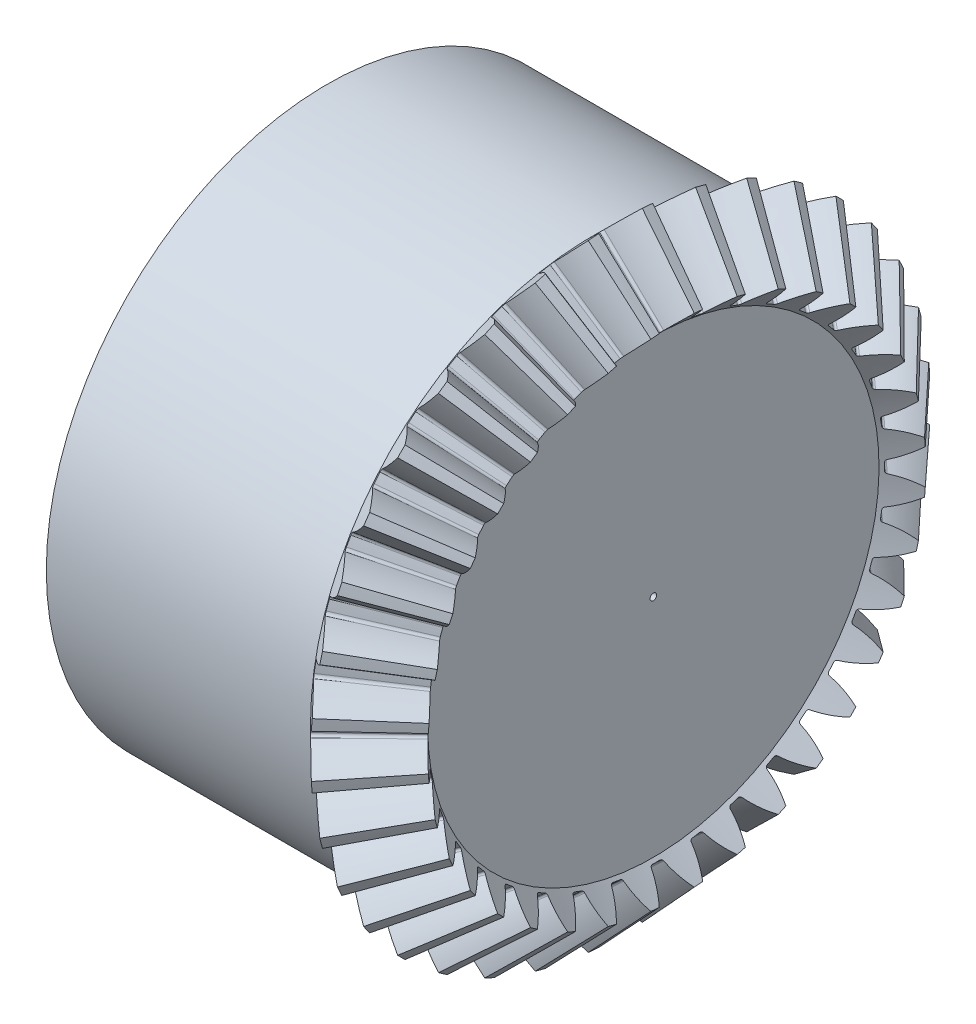
SolidWorks part; units mm, degrees
revolve "Base-Revolve" add sketch "BasProSke" angle 360 about L0 other way angle 5
sketch "BasProSke" plane through (0, 0, 0) normal (0, 1, 0) x (1, 0, 0)
  line L0 (-10, 0) -> (60, 0) construction
  line L1 (0, 0) -> (0, 33.899)
  line L2 (0, 0) -> (7.4837, 0)
  line L3 (7.4837, 0) -> (7.4837, 27.2406)
  line L4 (38.101, 0) -> (-20.321, 58.422) construction
  line L5 (0, 33.899) -> (3.5152, 37.4142)
  line L6 (38.101, 0) -> (-41.3373, 85.9348) construction
  line L7 (38.101, 0) -> (0, 33.899) construction
  line L8 (3.5152, 37.4142) -> (10.3085, 30.0654)
  line L9 (10.3085, 30.0654) -> (7.4837, 27.2406)
  line L10 (2.101, 36) -> (-9.8834, 36) construction
  dimension "D1" = 67.798
  dimension "D2" = 38.101
  dimension "D3" = 50.9117
  dimension "D4" = 2.25
ref_plane "Plane1" through (0, 0, 0) normal (0, 0, 1) x (1, 0, 0)
ref_plane "Plane2" through (0, 0, 0) normal (0, 1, 0) x (1, 0, 0)
ref_plane "Plane3" through (0, 0, 0) normal (1, 0, 0) x (0, 0, -1)
sketch "HoldingSke" plane through (0, 0, 0) normal (0, 1, 0) x (1, 0, 0)
  line L0 (0, 0) -> (0.4045, -0.2939)
  line L1 (-15, 0) -> (100, 0) construction
  line L2 (0, 0) -> (-69.4833, 60.7542)
  line L3 (0, 0) -> (-11.863, 4.5341)
  line L4 (0, 0) -> (6.9867, 5.0761)
  line L5 (0, 0) -> (-65.5867, -24.4619)
  line L6 (0, 0) -> (-10.5278, -7.1032)
  line L7 (-69.4833, 60.7542) -> (-40.5324, 124.4869)
  line L8 (-76.2, 2) -> (-76.1, 2)
  line L9 (-71.009, 38.7566) -> (-53.1078, 45.2721)
  line L10 (-76.2, 71.12) -> (104.1128, 71.12)
  line L11 (0, 0) -> (-10, 0)
  line L12 (-76.2, 101.6) -> (-76.133, 101.6)
  line L13 (24.9733, 27.94) -> (52.9518, 28.4284)
  line L14 (24.9733, 27.94) -> (24.9743, 27.94)
  line L15 (24.9733, 27.94) -> (100.4024, 29.5042)
  line L16 (-69.4833, 60.7542) -> (34.9667, -15.1332)
  circle A0 centre (0, 0) radius 0.4
  circle A1 centre (0, 0) radius 33.899
  circle A2 centre (0, 0) radius 37.5
  circle A3 centre (0, 0) radius 0.4
  dimension "Num_teeth" = 36
  dimension "Pitch_radius" = 180.3128
  dimension "Width" = 10
ref_plane "ToothPln" through (1.7576, 35.6566, 0) normal (-0.7071, 0.7071, 0) x (0, 0, -1)
ref_plane "ToothPln2" through (19.0505, -19.0505, 0) normal (-0.7071, 0.7071, 0) x (0, 0, 1)
sketch "TooCutSke" plane through (1.7576, 35.6566, 0) normal (-0.7071, 0.7071, 0) x (0, 0, -1)
  line L2 (0, 35.5144) -> (147.7559, -1653.3434) construction
  line L3 (0, 35.5144) -> (80.057, -1759.7192) construction
  line L4 (0, -15.621) -> (0, 105.791) construction
  line L6 (-24.765, -2.4856) -> (21.082, -2.4856) construction
  line L7 (3.1376, -0.3486) -> (1.6023, -0.4171) construction
  arc A0 (-3.0922, -3.1221) -> (3.0922, -3.1221) centre (0, 35.5144) ccw
  arc A1 (-0.5546, 1.8959) -> (0.5546, 1.8959) centre (0, 35.5144) ccw
  circle A2 centre (0, 35.5144) radius 36 construction
  circle A3 centre (0, 35.5144) radius 33.8289 construction
  arc A4 (0.9263, 1.6113) -> (0.5546, 1.8959) centre (0.5608, 1.519) ccw
  arc A5 (0.9263, 1.6113) -> (3.0922, -3.1221) centre (14.8879, 5.1376) ccw
  arc A6 (-3.0922, -3.1221) -> (-0.9263, 1.6113) centre (-14.8879, 5.1376) ccw
  arc A7 (-0.5546, 1.8959) -> (-0.9263, 1.6113) centre (-0.5608, 1.519) ccw
  ellipse E0 centre (0, 23.9702) end of major axis (37.4142, 23.9702) minor radius 26.4558 construction
sketch "TooCutSke2" plane through (19.0505, -19.0505, 0) normal (-0.7071, 0.7071, 0) x (0, 0, 1)
  line L0 (0, 0) -> (0, 68.072) construction
  line L2 (21.082, 23.9702) -> (-20.32, 23.9702) construction
  circle A0 centre (0, 26.9415) radius 0.0127
  ellipse E1 centre (0, 0) end of major axis (-33.899, 0) minor radius 23.9702 construction
loft "ToothCut" cut profiles "TooCutSke2", "TooCutSke"
pattern_circular "TeethCuts" count 36 every 10 about axis through (-10, 0, 0) along (1, 0, 0) of "ToothCut"
sketch "HubSke" plane through (0, 0, 0) normal (-1, 0, 0) x (0, 0, 1)
  circle A0 centre (0, 0) radius 33.899
  dimension "Diameter" = 67.798
extrude "Hub" add sketch "HubSke" along normal blind 31.8991
sketch "BorSke" plane through (0, 0, 0) normal (1, 0, 0) x (0, 0, -1)
  circle A0 centre (0, 0) radius 0.4
  dimension "Diameter" = 0.8
extrude "Bore" cut sketch "BorSke" along normal mid plane 140.0001
sketch "KeySke" plane through (0, 0, 0) normal (1, 0, 0) x (0, 0, -1)
  line L0 (-0.05, 0) -> (-0.05, 0.5)
  line L1 (-0.05, 0.5) -> (0.05, 0.5)
  line L2 (0.05, 0.5) -> (0.05, 0)
  line L3 (0, 0) -> (0, 34) construction
  line L4 (-0.05, 0) -> (0.05, 0)
  dimension "Offset" = 0.5
extrude "Keyway" [suppressed] cut sketch "KeySke" along normal mid plane 140.0001
pattern_circular "Keyway2" [suppressed] count 2 every 90 about axis through (-10, 0, 0) along (1, 0, 0) reverse direction yes
equation "' \"Module@HoldingSke\" = 6.35"
equation "' \"Num_teeth@HoldingSke\" = 12"
equation "' \"Mating_teeth@HoldingSke\" = 12"
equation "' \"Ap@HoldingSke\" =  20"
equation "' \"Ap@HoldingSke\" = 20"
equation "' \"Width@HoldingSke\" = 0.5 * 25.4"
equation "' \"Hub_dia@HoldingSke\"= 2 * 25.4"
equation "' \"Hub_dia@HoldingSke\" = 2 * 25.4"
equation "' \"Mounting_dist@HoldingSke\" = 2 * 25.4"
equation "' \"Bore@HoldingSke\" = 19"
equation "' \"T_dim@HoldingSke\" = 0.1 * 25.4"
equation "' \"Width@KeySke\" = 0.25 * 25.4"
equation "' \"Show_teeth@HoldingSke\" = 100"
equation "' \"Backlash@HoldingSke\" = 0.009 * 25.4"
equation "' \"Addendum_fac@HoldingSke\" = 1.0"
equation "' \"Dedendum_fac@HoldingSke\" = 1.188"
equation "' \"Dedendum_add@HoldingSke\" = 0.002 * 25.4"
equation "' \"Clearance_fac@HoldingSke\" = 0.188"
equation "\"Pitch@HoldingSke\" = 1 / \"Module@HoldingSke\""
equation "' \"Addendum_fac@HoldingSke\" = 0.54 + 0.46 / (\"Num_teeth@HoldingSke\" /  \"Mating_teeth@HoldingSke\" ) ^ 2"
equation " \"Addendum_fac@HoldingSke\" = 2 - (0.54 + 0.46 / (\"Mating_teeth@HoldingSke\" /  \"Num_teeth@HoldingSke\" ) ^ 2)"
equation "\"Dedendum_fac@HoldingSke\" = 2.188 - \"Addendum_fac@HoldingSke\""
equation "\"Pitch_rad@BasProSke\" = \"Num_teeth@HoldingSke\" / \"Pitch@HoldingSke\" / 2"
equation "\"Pitch_ang@BasProSke\" = atn(\"Num_teeth@HoldingSke\" / \"Mating_teeth@HoldingSke\") * (180 / 3.14159265)"
equation "\"Addendum@BasProSke\" = \"Addendum_fac@HoldingSke\" / \"Pitch@HoldingSke\""
equation "\"Dedendum_plus@BasProSke\" = (\"Dedendum_fac@HoldingSke\" / \"Pitch@HoldingSke\" + \"Dedendum_add@HoldingSke\") * 1.25"
equation "\"Face_wid@BasProSke\" = \"Width@HoldingSke\""
equation "\"Radius@TooCutSke\" = ((\"Num_teeth@HoldingSke\" + 2 * \"Addendum_fac@HoldingSke\") / \"Pitch@HoldingSke\" ) / 2"
equation "\"Overcut_dia@TooCutSke\" =  1.02 * (\"Num_teeth@HoldingSke\" + 2 * \"Addendum_fac@HoldingSke\") / \"Pitch@HoldingSke\""
equation "\"Pitch_dia@TooCutSke\" = \"Num_teeth@HoldingSke\" / \"Pitch@HoldingSke\""
equation "\"Base_dia@TooCutSke\" = \"Num_teeth@HoldingSke\" / \"Pitch@HoldingSke\" * cos((\"Ap@HoldingSke\"  * 3.14159265 / 180))"
equation "'  \"Root_dia@TooCutSke\" =  (\"Num_teeth@HoldingSke\" + 2) / \"Pitch@HoldingSke\" - 2 * (\"Addendum_fac@HoldingSke\" + \"Dedendum_fac@HoldingSke\") / \"Pitch@HoldingSke\" - \"Dedendum_add@HoldingSke\" * 2"
equation "'  \"Root_dia@TooCutSke\" = (\"Num_teeth@HoldingSke\" + 2) / \"Pitch@HoldingSke\" - 2 * (\"Addendum_fac@HoldingSke\" + \"Dedendum_fac@HoldingSke\") / \"Pitch@HoldingSke\" - \"Dedendum_add@HoldingSke\" * 2"
equation "\"Root_dia@TooCutSke\" =  \"Num_teeth@HoldingSke\" / \"Pitch@HoldingSke\" -  2 * \"Dedendum_fac@HoldingSke\" / \"Pitch@HoldingSke\" - \"Dedendum_add@HoldingSke\" * 2"
equation "\"Half_ang@TooCutSke\" = 180 / \"Num_teeth@HoldingSke\""
equation "\"Half_CT@TooCutSke\" = \"Num_teeth@HoldingSke\" / \"Pitch@HoldingSke\" * sin((3.14159265 / 2 / \"Num_teeth@HoldingSke\")) / 2 - 2 * \"Backlash@HoldingSke\" / 4"
equation "\"Flank_rad@TooCutSke\" = \"Num_teeth@HoldingSke\" / \"Pitch@HoldingSke\" / 5"
equation "\"Root_fillet@TooCutSke\" = \"Clearance_fac@HoldingSke\" / \"Pitch@HoldingSke\" + \"Dedendum_add@HoldingSke\""
equation "\"Offset@ToothPln2\"  = \"Num_teeth@HoldingSke\" / \"Pitch@HoldingSke\" / 2 / sin(atn(\"Num_teeth@HoldingSke\" / \"Mating_teeth@HoldingSke\"))"
equation "\"Dedendum_plus@TooCutSke2\" = \"Dedendum_plus@BasProSke\""
equation "\"MHD@HoldingSke\" = \"Num_teeth@HoldingSke\" / \"Pitch@HoldingSke\" - 2 * \"Dedendum_plus@BasProSke\" * cos(atn(\"Num_teeth@HoldingSke\" / \"Mating_teeth@HoldingSke\"))"
equation "\"MBD@HoldingSke\" = \"Num_teeth@HoldingSke\" / \"Pitch@HoldingSke\" - 2 * \"Dedendum_plus@BasProSke\" * cos(atn(\"Num_teeth@HoldingSke\" / \"Mating_teeth@HoldingSke\")) - 0.002 * 25.4"
equation "\"MnMD@HoldingSke\" =  \"Num_teeth@HoldingSke\" / \"Pitch@HoldingSke\" / 2 / (\"Num_teeth@HoldingSke\" / \"Mating_teeth@HoldingSke\") + \"Dedendum_plus@BasProSke\" * sin(atn(\"Num_teeth@HoldingSke\" / \"Mating_teeth@HoldingSke\"))"
equation "\"OAL@HoldingSke\" = \"MnMD@HoldingSke\""
equation "\"MHD@HoldingSke\" = ((sgn( \"MHD@HoldingSke\" - \"Hub_dia@HoldingSke\" )-1)*( \"MHD@HoldingSke\" - \"Hub_dia@HoldingSke\" ))/-2+ \"Hub_dia@HoldingSke\""
equation "\"MBD@HoldingSke\" = ((sgn( \"MBD@HoldingSke\" - \"Bore@HoldingSke\" )-1)*( \"MBD@HoldingSke\" - \"Bore@HoldingSke\" ))/-2+ \"Bore@HoldingSke\""
equation "\"Face_wid@BasProSke\" = ((sgn( \"Face_wid@BasProSke\" - \"Offset@ToothPln2\" * 0.9)-1)*( \"Face_wid@BasProSke\" - \"Offset@ToothPln2\" * 0.9))/-2+ \"Offset@ToothPln2\" * 0.9"
equation "\"OAL@HoldingSke\" = ((sgn( \"OAL@HoldingSke\" - \"Mounting_dist@HoldingSke\" )+1)*( \"OAL@HoldingSke\" - \"Mounting_dist@HoldingSke\" ))/2 + \"Mounting_dist@HoldingSke\" + 0.000002 * 25.4"
equation "\"Num_teeth@TeethCuts\" = int( \"Show_teeth@HoldingSke\" ) + 1"
equation "\"Num_teeth@TeethCuts\" = ((sgn( \"Num_teeth@TeethCuts\" - \"Num_teeth@HoldingSke\" )-1)*( \"Num_teeth@TeethCuts\" - \"Num_teeth@HoldingSke\" ))/-2+ \"Num_teeth@HoldingSke\""
equation "\"Num_teeth@TeethCuts\" = ((sgn( \"Num_teeth@TeethCuts\" - 2.0)+1)*( \"Num_teeth@TeethCuts\" - 2.0))/2 +2.0"
equation "\"Angle@TeethCuts\" = 360.0 / \"Num_teeth@HoldingSke\""
equation "\"Diameter@HubSke\" = \"MHD@HoldingSke\""
equation "\"Length@Hub\" = \"OAL@HoldingSke\" - \"MnMD@HoldingSke\" + 0.000002 * 25.4"
equation "\"Diameter@BorSke\" = \"MBD@HoldingSke\""
equation "\"D1@Bore\" = \"OAL@HoldingSke\" * 2.0"
equation "\"D1@Keyway\" = \"OAL@HoldingSke\" * 2.0"
equation "\"Offset@KeySke\" = \"T_dim@HoldingSke\" + \"MBD@HoldingSke\" / 2.0"
